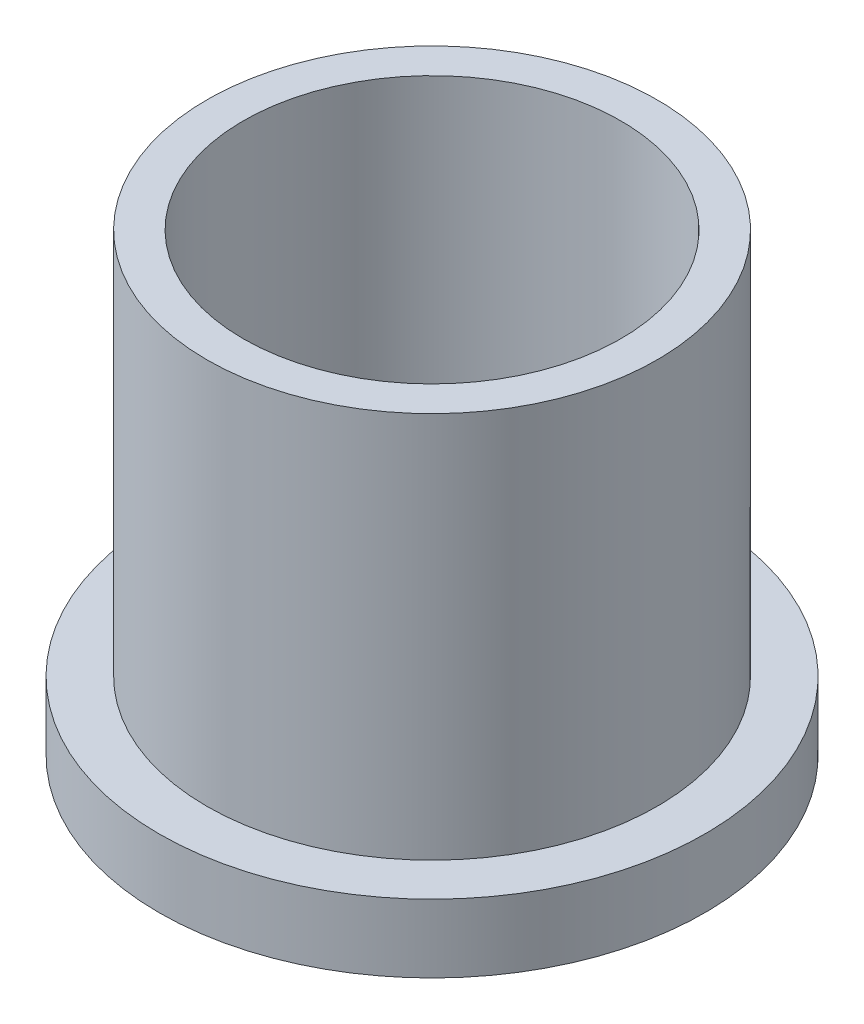
SolidWorks part; units mm, degrees
ref_plane "Alzado" through (0, 0, 0) normal (0, 0, 1) x (1, 0, 0)
ref_plane "Planta" through (0, 0, 0) normal (0, 1, 0) x (1, 0, 0)
ref_plane "Vista lateral" through (0, 0, 0) normal (1, 0, 0) x (0, 0, -1)
sketch "Croquis1" plane through (0, 0, 0) normal (0, 1, 0) x (1, 0, 0)
  circle A0 centre (0, 0) radius 4.95
  circle A1 centre (0, 0) radius 4.15
  circle A2 centre (0, 0) radius 6
  dimension "D1" = 9.9
  dimension "D2" = 8.3
  dimension "D3" = 12
extrude "Saliente-Extruir1" add sketch "Croquis1" along normal blind 10 contours A0 A1 region at (-4.81, 0, 0)
extrude "Saliente-Extruir2" add sketch "Croquis1<3>" along normal blind 1.5 contours A2 A0 region at (-5.8303, 0, 0)
sketch "Croquis1<3>" plane through (0, 0, 0) normal (0, 1, 0) x (1, 0, 0) same geometry as "Croquis1"
